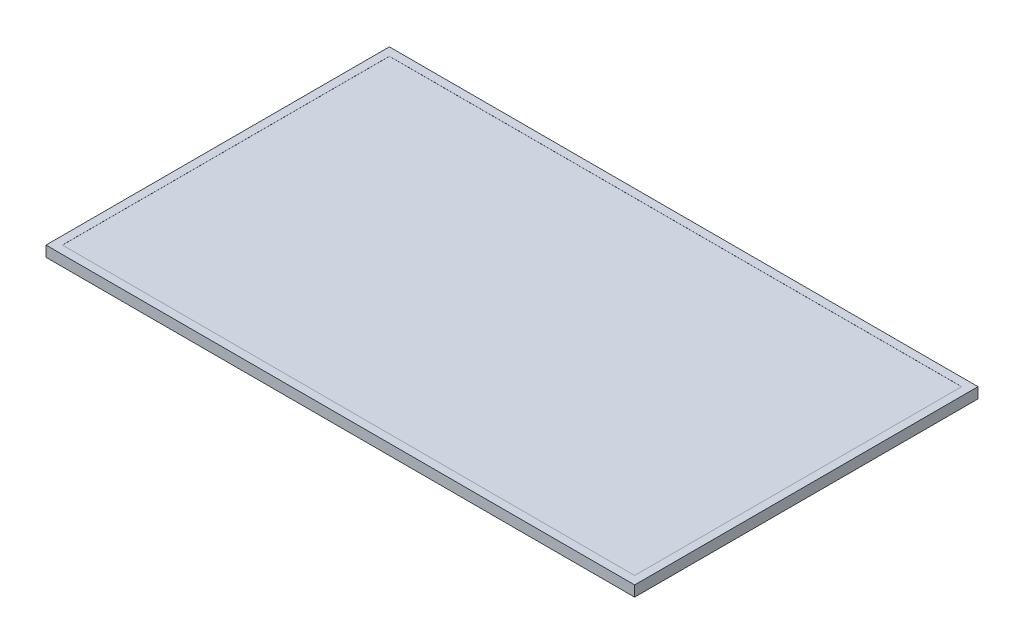
SolidWorks part; units mm, degrees
ref_plane "Front Plane" through (0, 0, 0) normal (0, 0, 1) x (1, 0, 0)
ref_plane "Top Plane" through (0, 0, 0) normal (0, 1, 0) x (1, 0, 0)
ref_plane "Right Plane" through (0, 0, 0) normal (1, 0, 0) x (0, 0, -1)
sketch "Sketch1" plane through (0, 0, 0) normal (0, 1, 0) x (1, 0, 0)
  line L1 (-180, -105) -> (180, -105)
  line L2 (-180, -105) -> (-180, 105)
  line L3 (-180, 105) -> (180, 105)
  line L4 (180, -105) -> (180, 105)
  line L5 (-180, -105) -> (180, 105) construction
  line L6 (-180, 105) -> (180, -105) construction
  line L7 (-175, -100) -> (175, -100)
  line L8 (-175, -100) -> (-175, 100)
  line L9 (-175, 100) -> (175, 100)
  line L10 (175, -100) -> (175, 100)
  line L11 (-175, -100) -> (175, 100) construction
  line L12 (-175, 100) -> (175, -100) construction
  line L13 (47, -72.4) -> (75, -72.4)
  line L14 (47, -72.4) -> (47, -65.4)
  line L15 (47, -65.4) -> (75, -65.4)
  line L16 (75, -72.4) -> (75, -65.4)
  point P0 (0, 0)
  point P6 (0, 0)
  dimension "D1" = 360
  dimension "D2" = 210
  dimension "D3" = 5
  dimension "D4" = 5
  dimension "D5" = 28
  dimension "D6" = 7
  dimension "D7" = 105
  dimension "D8" = 32.6
extrude "Boss-Extrude3" add sketch "Sketch1" along normal blind 6.45 contours L7 L10 L9 L8 L16 L13 L14 L15 | L13 L16 L15 L14 region at (-0.1713, 0, -0.1935) region at (61, 0, 68.9)
extrude "Boss-Extrude4" add sketch "Sketch1<4>" along normal blind 6.5 contours L1 L4 L3 L2 L10 L7 L8 L9 region at (-175.8323, 0, 0)
sketch "Sketch1<4>" plane through (0, 0, 0) normal (0, 1, 0) x (1, 0, 0) same geometry as "Sketch1"
extrude "Boss-Extrude5" add sketch "Sketch1<5>" against normal blind 0.5 contours L13 L16 L15 L14 region at (61, 0, 68.9)
sketch "Sketch1<5>" plane through (0, 0, 0) normal (0, 1, 0) x (1, 0, 0) same geometry as "Sketch1"
